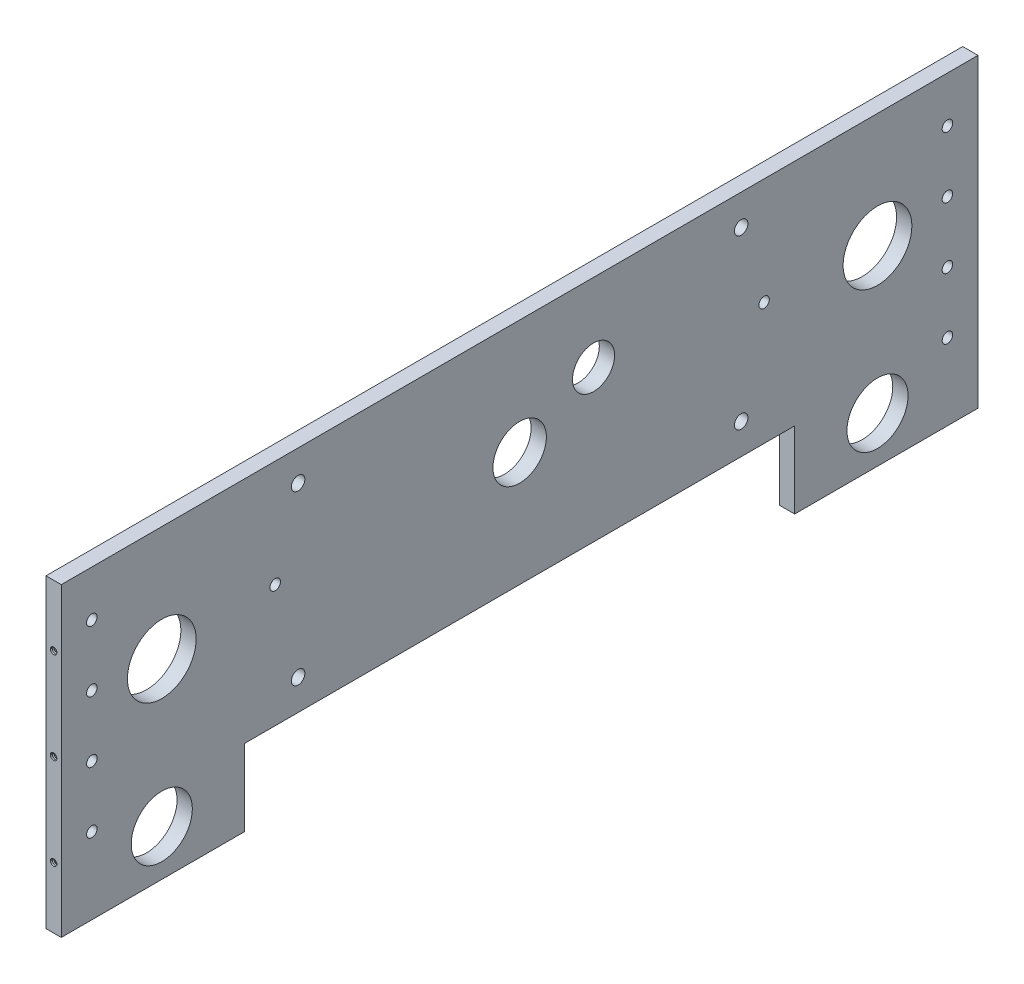
SolidWorks part; units mm, degrees
material "6061-T6 (SS)"
ref_plane "Front Plane" through (0, 0, 0) normal (0, 0, 1) x (1, 0, 0)
ref_plane "Top Plane" through (0, 0, 0) normal (0, 1, 0) x (1, 0, 0)
ref_plane "Right Plane" through (0, 0, 0) normal (1, 0, 0) x (0, 0, -1)
sketch "Sketch1" plane through (0, 0, 0) normal (1, 0, 0) x (0, 0, -1)
  line L1 (-190.5, 63.5) -> (190.5, 63.5)
  line L2 (-190.5, 63.5) -> (-190.5, -63.5)
  line L3 (-190.5, -63.5) -> (190.5, -63.5)
  line L4 (190.5, 63.5) -> (190.5, -63.5)
  line L5 (-190.5, 63.5) -> (190.5, -63.5) construction
  line L6 (-190.5, -63.5) -> (190.5, 63.5) construction
  point P0 (0, 0)
  dimension "D1" = 127
  dimension "D2" = 381
extrude "Boss-Extrude1" add sketch "Sketch1" along normal blind 6.35
sketch "Sketch2" plane through (6.35, 0, 0) normal (1, 0, 0) x (0, 0, -1)
  line L0 (-190.5, -63.5) -> (190.5, -63.5) construction
  line L1 (-148.7297, 15.875) -> (0, 15.875) construction
  line L2 (-74.3648, -34.925) -> (-74.3648, 15.875) construction
  line L3 (0, 15.875) -> (148.7297, 15.875) construction
  line L4 (74.3648, -34.925) -> (74.3648, 15.875) construction
  line L5 (190.5, 63.5) -> (-190.5, 63.5) construction
  line L6 (65.278, 53.34) -> (-56.642, 53.34) construction
  line L7 (65.278, 53.34) -> (65.278, -13.97) construction
  line L8 (65.278, -13.97) -> (-56.642, -13.97) construction
  line L9 (-56.642, 53.34) -> (-56.642, -13.97) construction
  line L10 (-190.5, -63.5) -> (190.5, -63.5) construction
  circle A1 centre (-148.7297, 15.875) radius 14.2875
  circle A2 centre (148.7297, 15.875) radius 14.2875
  circle A3 centre (-148.7297, 15.875) radius 38.1 construction
  circle A4 centre (0, 15.875) radius 38.1 construction
  circle A5 centre (148.7297, 15.875) radius 38.1 construction
  circle A6 centre (-74.3648, -34.925) radius 6.35 construction
  circle A7 centre (74.3648, -34.925) radius 6.35 construction
  circle A8 centre (-74.3648, 9.525) radius 6.35 construction
  circle A9 centre (74.3648, 9.525) radius 6.35 construction
  circle A11 centre (-148.7297, -44.4161) radius 12.7
  circle A12 centre (148.7297, -44.4161) radius 12.7
  circle A13 centre (0, 15.875) radius 29.21 construction
  circle A14 centre (30.7172, 31.115) radius 5.08 construction
  circle A15 centre (30.7172, 31.115) radius 8.75
  circle A16 centre (0, 15.875) radius 11.1125
  point P11 (0, 0)
  dimension "D1" = 28.575
  dimension "D5" = 76.2
  dimension "D7" = 12.7
  dimension "D14" = 25.4
  dimension "D15" = 19.0839
  dimension "D17" = 25.4
  dimension "D20" = 58.42
  dimension "D21" = 10.16
  dimension "D22" = 17.5001
  dimension "D24" = 22.225
  dimension "D25" = 28.575
  dimension "D2" = 79.375
  dimension "D3" = 148.7297
  dimension "D4" = 148.7297
  dimension "D6" = 0
  dimension "D8" = 28.575
  dimension "D9" = 44.45
  dimension "D10" = 56.642
  dimension "D11" = 121.92
  dimension "D12" = 10.16
  dimension "D13" = 49.53
  dimension "D16" = 148.7297
  dimension "D18" = 19.0839
  dimension "D19" = 148.7297
  dimension "D23" = 15.24
extrude "Cut-Extrude1" cut sketch "Sketch2" against normal through all
sketch "Sketch3" plane through (6.35, 0, 0) normal (1, 0, 0) x (0, 0, -1)
  line L0 (-184.404, 19.05) -> (-184.404, -19.05) construction
  line L1 (-190.5, 63.5) -> (-190.5, -63.5) construction
  point P2 (-184.404, 0)
  point P3 (-190.5, 0)
  dimension "D1" = 38.1
  dimension "D2" = 6.096
sketch "Sketch23" plane through (6.35, 0, 0) normal (1, 0, 0) x (0, 0, -1)
  line L0 (-114.3, -63.5) -> (-114.3, -31.75)
  line L1 (-190.5, -63.5) -> (190.5, -63.5) construction
  line L2 (-114.3, -31.75) -> (114.3, -31.75)
  line L3 (114.3, -31.75) -> (114.3, -63.5)
  line L4 (-190.5, 63.5) -> (-190.5, -63.5) construction
  line L5 (190.5, -63.5) -> (190.5, 63.5) construction
  line L6 (-114.3, -63.5) -> (114.3, -63.5)
  dimension "D1" = 31.75
  dimension "D2" = 76.2
  dimension "D3" = 76.2
extrude "Cut-Extrude6" cut sketch "Sketch23" against normal through all
sketch "Sketch24" plane through (0, 0, 0) normal (-1, 0, 0) x (0, 0, 1)
  line L0 (-190.5, -63.5) -> (-190.5, 63.5) construction
  line L1 (-190.5, 63.5) -> (190.5, 63.5) construction
  point P0 (-92.075, -19.05)
  point P1 (-92.075, 50.8)
  point P2 (92.075, -19.05)
  point P4 (92.075, 50.8)
  dimension "D1" = 69.85
  dimension "D2" = 98.425
  dimension "D3" = 12.7
  dimension "D4" = 12.7
  dimension "D5" = 69.85
  dimension "D6" = 184.15
hole_wizard "CSK for #10 Flat Head Machine Screw2" positions "Sketch25" profile "Sketch26" countersink size "#10" standard "ANSI Inch" end condition through all
sketch "Sketch25" plane through (0, 0, 0) normal (-1, 0, 0) x (0, 0, 1)
  point P0 (-92.075, 50.8)
  point P3 (-92.075, -19.05)
  point P6 (92.075, -19.05)
  point P9 (92.075, 50.8)
sketch "Sketch26" plane through (0, 50.8, -92.075) normal (0, 1, 0) x (0, 0, 1)
  line L0 (0, 0) -> (0, 6.35)
  line L1 (0, 6.35) -> (2.8067, 6.35)
  line L2 (2.8067, 6.35) -> (2.8067, 2.396)
  line L3 (2.8067, 2.396) -> (4.8895, 0)
  line L5 (4.8895, 0) -> (0, 0)
  line L6 (-2.8067, 2.396) -> (-4.8895, 0) construction
  line L11 (0, -6.35) -> (0, 107.95) construction
  dimension "Thru Hole Dia." = 5.6134
  dimension "Thru Hole Depth" = 6.35
  dimension "Near C'Sink Dia." = 9.779
  dimension "Near C'Sink Angle" = 82
sketch "Sketch27" plane through (6.35, 0, 0) normal (1, 0, 0) x (0, 0, -1)
  line L0 (190.5, -63.5) -> (190.5, 63.5) construction
  line L1 (114.3, -63.5) -> (190.5, -63.5) construction
  line L2 (-190.5, -63.5) -> (-114.3, -63.5) construction
  line L3 (-190.5, 63.5) -> (-190.5, -63.5) construction
  point P0 (177.8, -57.15)
  point P1 (177.8, -31.75)
  point P2 (177.8, -6.35)
  point P3 (177.8, 19.05)
  point P4 (177.8, 44.45)
  point P7 (-177.8, -57.15)
  point P8 (-177.8, -31.75)
  point P9 (-177.8, -6.35)
  point P10 (-177.8, 19.05)
  point P11 (-177.8, 44.45)
  dimension "D1" = 25.4
  dimension "D2" = 25.4
  dimension "D3" = 25.4
  dimension "D4" = 25.4
  dimension "D5" = 12.7
  dimension "D6" = 25.4
  dimension "D7" = 25.4
  dimension "D8" = 25.4
  dimension "D9" = 25.4
  dimension "D10" = 6.35
  dimension "D11" = 6.35
  dimension "D12" = 12.7
hole_wizard "11/64 (0.17188) Diameter Hole1" positions "Sketch28" profile "Sketch29" hole size "11/64" standard "ANSI Inch" end condition through all
sketch "Sketch28" plane through (6.35, 0, 0) normal (1, 0, 0) x (0, 0, -1)
  point P0 (-177.8, 44.45)
  point P3 (-177.8, 19.05)
  point P6 (-177.8, -6.35)
  point P9 (-177.8, -31.75)
  point P12 (177.8, -31.75)
  point P15 (177.8, -6.35)
  point P18 (177.8, 19.05)
  point P21 (177.8, 44.45)
sketch "Sketch29" plane through (6.35, 44.45, 177.8) normal (0, 1, 0) x (0, 0, -1)
  line L0 (0, 0) -> (0, 6.35)
  line L1 (0, 6.35) -> (2.1829, 6.35)
  line L2 (2.1829, 6.35) -> (2.1829, 0)
  line L5 (2.1829, 0) -> (0, 0)
  line L11 (0, -6.35) -> (0, 107.95) construction
  dimension "Thru Hole Dia." = 4.3658
  dimension "Thru Hole Depth" = 6.35
sketch "Sketch30" plane through (6.35, 0, 0) normal (1, 0, 0) x (0, 0, -1)
  line L0 (-190.5, 63.5) -> (-190.5, -63.5) construction
  line L1 (190.5, -63.5) -> (190.5, 63.5) construction
  line L2 (190.5, 63.5) -> (-190.5, 63.5) construction
  point P0 (-101.6, 19.05)
  point P1 (101.6, 19.05)
  dimension "D1" = 88.9
  dimension "D2" = 88.9
  dimension "D3" = 44.45
hole_wizard "11/64 (0.17188) Diameter Hole2" positions "Sketch31" profile "Sketch32" hole size "11/64" standard "ANSI Inch"
sketch "Sketch31" plane through (6.35, 0, 0) normal (1, 0, 0) x (0, 0, -1)
  point P0 (-101.6, 19.05)
  point P3 (101.6, 19.05)
sketch "Sketch32" plane through (6.35, 19.05, 101.6) normal (0, 1, 0) x (0, 0, -1)
  line L0 (0, 0) -> (0, 10.2016)
  line L1 (0, 10.2016) -> (2.1829, 8.89)
  line L2 (2.1829, 8.89) -> (2.1829, 0)
  line L5 (2.1829, 0) -> (0, 0)
  line L10 (0, 10.2016) -> (-2.1829, 8.89) construction
  line L11 (0, -6.35) -> (0, 107.95) construction
  dimension "Hole Dia." = 4.3658
  dimension "Hole Depth" = 8.89
  dimension "Drill Angle" = 118
sketch "Sketch33" plane through (0, 0, 190.5) normal (0, 0, 1) x (1, 0, 0)
  line L0 (6.35, 63.5) -> (0, 63.5) construction
  line L1 (0, 63.5) -> (0, -63.5) construction
  point P0 (3.175, 38.1)
  point P1 (3.175, 0)
  point P2 (3.175, -38.1)
  dimension "D1" = 25.4
  dimension "D2" = 3.175
  dimension "D3" = 38.1
  dimension "D4" = 38.1
hole_wizard "#36 (0.1065) Diameter Hole1" positions "Sketch34" profile "Sketch35" hole size "#36" standard "ANSI Inch"
sketch "Sketch34" plane through (0, 0, 190.5) normal (0, 0, 1) x (1, 0, 0)
  point P0 (3.175, 38.1)
  point P3 (3.175, -38.1)
  point P6 (3.175, 0)
sketch "Sketch35" plane through (3.175, 38.1, 190.5) normal (1, 0, 0) x (0, -1, 0)
  line L0 (0, 0) -> (0, 9.7027)
  line L1 (0, 9.7027) -> (1.3525, 8.89)
  line L2 (1.3525, 8.89) -> (1.3525, 0)
  line L5 (1.3525, 0) -> (0, 0)
  line L10 (0, 9.7027) -> (-1.3525, 8.89) construction
  line L11 (0, -6.35) -> (0, 107.95) construction
  dimension "Hole Dia." = 2.7051
  dimension "Hole Depth" = 8.89
  dimension "Drill Angle" = 118
thread "Thread1" pitch 0.7937 method cut profile "Thread Profile1" start angle 0, offset 0, length 6.35, pitch 0.7937, diameter 2.7051
ref_plane "Plane1" through (1.8225, 38.1, 190.5) normal (0, -1, 0) x (-1, 0, 0)
sketch "Thread Profile1" plane through (1.8225, 38.1, 190.5) normal (0, -1, 0) x (-1, 0, 0)
  line L0 (0, 0) -> (0, 0.7937) construction
  line L1 (0, 0) -> (0.4296, 0.248)
  line L2 (0.4296, 0.248) -> (0.4296, 0.3473)
  line L3 (0.4296, 0.3473) -> (0, 0.5953)
  line L4 (0.4296, 0.2977) -> (0, 0.2977) construction
  line L11 (0, 0) -> (0, 0.5953)
  point P2 (0, 0)
  dimension "Pitch" = 0.7937
  dimension "Profile_Angle" = 60
  dimension "Profile_Land" = 0.0992
  dimension "Profile_Height" = 0.4296
thread "Thread2" pitch 0.7937 method cut profile "Thread Profile2" start angle 0, offset 0, length 6.35, pitch 0.7937, diameter 2.7051
ref_plane "Plane2" through (1.8225, 0, 190.5) normal (0, -1, 0) x (-1, 0, 0)
sketch "Thread Profile2" plane through (1.8225, 0, 190.5) normal (0, -1, 0) x (-1, 0, 0)
  line L0 (0, 0) -> (0, 0.7937) construction
  line L1 (0, 0) -> (0.4296, 0.248)
  line L2 (0.4296, 0.248) -> (0.4296, 0.3473)
  line L3 (0.4296, 0.3473) -> (0, 0.5953)
  line L4 (0.4296, 0.2977) -> (0, 0.2977) construction
  line L11 (0, 0) -> (0, 0.5953)
  point P2 (0, 0)
  dimension "Pitch" = 0.7937
  dimension "Profile_Angle" = 60
  dimension "Profile_Land" = 0.0992
  dimension "Profile_Height" = 0.4296
thread "Thread3" pitch 0.7937 method cut profile "Thread Profile3" start angle 0, offset 0, length 6.35, pitch 0.7937, diameter 2.7051
ref_plane "Plane3" through (1.8225, -38.1, 190.5) normal (0, -1, 0) x (-1, 0, 0)
sketch "Thread Profile3" plane through (1.8225, -38.1, 190.5) normal (0, -1, 0) x (-1, 0, 0)
  line L0 (0, 0) -> (0, 0.7937) construction
  line L1 (0, 0) -> (0.4296, 0.248)
  line L2 (0.4296, 0.248) -> (0.4296, 0.3473)
  line L3 (0.4296, 0.3473) -> (0, 0.5953)
  line L4 (0.4296, 0.2977) -> (0, 0.2977) construction
  line L11 (0, 0) -> (0, 0.5953)
  point P2 (0, 0)
  dimension "Pitch" = 0.7937
  dimension "Profile_Angle" = 60
  dimension "Profile_Land" = 0.0992
  dimension "Profile_Height" = 0.4296
sketch "Sketch42" plane through (0, 0, -190.5) normal (0, 0, -1) x (-1, 0, 0)
  line L0 (-6.35, 63.5) -> (0, 63.5) construction
  line L2 (-6.35, -63.5) -> (-6.35, 63.5) construction
  point P0 (-3.175, 38.1)
  point P1 (-3.175, 0)
  point P2 (-3.175, -38.1)
  point P5 (0, 0)
  point P7 (1.2428, 39.3258)
  dimension "D1" = 25.4
  dimension "D2" = 3.175
hole_wizard "#36 (0.1065) Diameter Hole2" positions "Sketch43" profile "Sketch44" hole size "#36" standard "ANSI Inch"
sketch "Sketch43" plane through (0, 0, -190.5) normal (0, 0, -1) x (-1, 0, 0)
  point P0 (-3.175, 38.1)
  point P3 (-3.175, 0)
  point P6 (-3.175, -38.1)
sketch "Sketch44" plane through (3.175, 38.1, -190.5) normal (1, 0, 0) x (0, 1, 0)
  line L0 (0, 0) -> (0, 9.7027)
  line L1 (0, 9.7027) -> (1.3525, 8.89)
  line L2 (1.3525, 8.89) -> (1.3525, 0)
  line L5 (1.3525, 0) -> (0, 0)
  line L10 (0, 9.7027) -> (-1.3525, 8.89) construction
  line L11 (0, -6.35) -> (0, 107.95) construction
  dimension "Hole Dia." = 2.7051
  dimension "Hole Depth" = 8.89
  dimension "Drill Angle" = 118
thread "Thread4" pitch 0.7937 method cut profile "Thread Profile4" start angle 0, offset 0, length 6.35, pitch 0.7937, diameter 2.7051
ref_plane "Plane4" through (4.5275, 38.1, -190.5) normal (0, -1, 0) x (1, 0, 0)
sketch "Thread Profile4" plane through (4.5275, 38.1, -190.5) normal (0, -1, 0) x (1, 0, 0)
  line L0 (0, 0) -> (0, 0.7937) construction
  line L1 (0, 0) -> (0.4296, 0.248)
  line L2 (0.4296, 0.248) -> (0.4296, 0.3473)
  line L3 (0.4296, 0.3473) -> (0, 0.5953)
  line L4 (0.4296, 0.2977) -> (0, 0.2977) construction
  line L11 (0, 0) -> (0, 0.5953)
  point P2 (0, 0)
  dimension "Pitch" = 0.7937
  dimension "Profile_Angle" = 60
  dimension "Profile_Land" = 0.0992
  dimension "Profile_Height" = 0.4296
thread "Thread5" pitch 0.7937 method cut profile "Thread Profile5" start angle 0, offset 0, length 6.35, pitch 0.7937, diameter 2.7051
ref_plane "Plane5" through (4.5275, 0, -190.5) normal (0, -1, 0) x (1, 0, 0)
sketch "Thread Profile5" plane through (4.5275, 0, -190.5) normal (0, -1, 0) x (1, 0, 0)
  line L0 (0, 0) -> (0, 0.7937) construction
  line L1 (0, 0) -> (0.4296, 0.248)
  line L2 (0.4296, 0.248) -> (0.4296, 0.3473)
  line L3 (0.4296, 0.3473) -> (0, 0.5953)
  line L4 (0.4296, 0.2977) -> (0, 0.2977) construction
  line L11 (0, 0) -> (0, 0.5953)
  point P2 (0, 0)
  dimension "Pitch" = 0.7937
  dimension "Profile_Angle" = 60
  dimension "Profile_Land" = 0.0992
  dimension "Profile_Height" = 0.4296
thread "Thread6" pitch 0.7937 method cut profile "Thread Profile6" start angle 0, offset 0, length 6.35, pitch 0.7937, diameter 2.7051
ref_plane "Plane6" through (4.5275, -38.1, -190.5) normal (0, -1, 0) x (1, 0, 0)
sketch "Thread Profile6" plane through (4.5275, -38.1, -190.5) normal (0, -1, 0) x (1, 0, 0)
  line L0 (0, 0) -> (0, 0.7937) construction
  line L1 (0, 0) -> (0.4296, 0.248)
  line L2 (0.4296, 0.248) -> (0.4296, 0.3473)
  line L3 (0.4296, 0.3473) -> (0, 0.5953)
  line L4 (0.4296, 0.2977) -> (0, 0.2977) construction
  line L11 (0, 0) -> (0, 0.5953)
  point P2 (0, 0)
  dimension "Pitch" = 0.7937
  dimension "Profile_Angle" = 60
  dimension "Profile_Land" = 0.0992
  dimension "Profile_Height" = 0.4296
